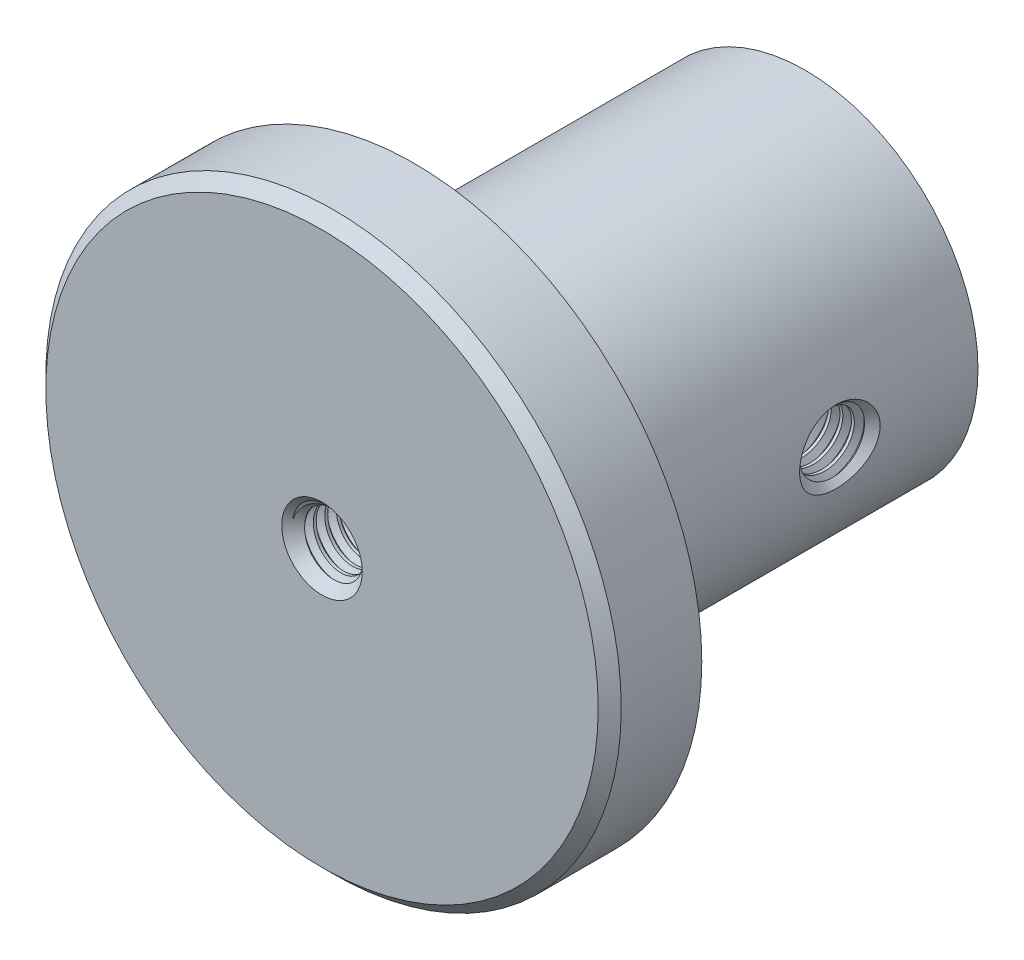
SolidWorks part; units mm, degrees
ref_plane "Front Plane" through (0, 0, 0) normal (0, 0, 1) x (1, 0, 0)
ref_plane "Top Plane" through (0, 0, 0) normal (0, 1, 0) x (1, 0, 0)
ref_plane "Right Plane" through (0, 0, 0) normal (1, 0, 0) x (0, 0, -1)
sketch "Sketch1" plane through (0, 0, 0) normal (0, 0, 1) x (1, 0, 0)
  circle A0 centre (0, 0) radius 12.5
  dimension "D1" = 25
extrude "Boss-Extrude1" add sketch "Sketch1" along normal blind 4
ref_axis "Axis1" through (0, 0, -0.35) along (0, 0, 1)
chamfer "Chamfer1" distance 0.5 angle 45 1 edges at (12.5, 0, 4)
ref_axis "Axis2" through (0, 14.0125, 4) along (0, -1, 0)
sketch "Sketch6" plane through (0, 0, 0) normal (1, 0, 0) x (0, 0, -1)
  line L0 (-4, 14.0125) -> (-4, -13.7625) construction
  line L1 (-4, 8.9) -> (-4, 11.1)
  line L2 (0, 12.5) -> (-3.5, 12.5) construction
  arc A0 (-4, 11.1) -> (-4, 8.9) centre (-4, 10) ccw
  dimension "D1" = 2.2
  dimension "D2" = 2.5
revolve "Cut-Revolve2" [suppressed] cut sketch "Sketch6" angle 360 about L1
pattern_circular "CirPattern1" [suppressed] count 15 over 360 of bodies 112
sketch "Sketch7" plane through (0, 0, 4) normal (0, 0, 1) x (1, 0, 0)
  circle A0 centre (0, 0) radius 1.25
  dimension "D1" = 2.5
extrude "Cut-Extrude1" cut sketch "Sketch7" against normal through all
thread "Thread1" pitch 0.5 method cut profile "Thread Profile1" start angle 0, offset 1, length 0, pitch 0.5, diameter 2.5
ref_plane "Plane1" through (-1.25, 0, 5) normal (0, -1, 0) x (-1, 0, 0)
sketch "Thread Profile1" plane through (-1.25, 0, 5) normal (0, -1, 0) x (-1, 0, 0)
  line L0 (0, 0) -> (0, 0.5) construction
  line L1 (0, 0) -> (0.2706, 0.1562)
  line L2 (0.2706, 0.1562) -> (0.2706, 0.2187)
  line L3 (0.2706, 0.2187) -> (0, 0.375)
  line L4 (0.2706, 0.1875) -> (0, 0.1875) construction
  line L11 (0, 0) -> (0, 0.375)
  point P2 (0, 0)
  dimension "Pitch" = 0.5
  dimension "Profile_Angle" = 60
  dimension "Profile_Land" = 0.0625
  dimension "Profile_Height" = 0.2706
sketch "Sketch10" plane through (0, 0, 4) normal (0, 0, 1) x (1, 0, 0)
  circle A0 centre (0, 0) radius 1.75
  dimension "D1" = 3.5
extrude "Cut-Extrude2" cut sketch "Sketch10" against normal blind 10 draft 45 contours A0
sketch "Sketch11" plane through (0, 0, 0) normal (0, 0, -1) x (-1, 0, 0)
  circle A0 centre (0, 0) radius 7.5
  dimension "D1" = 15
extrude "Boss-Extrude2" add sketch "Sketch11" along normal blind 17 contours A0
sketch "Sketch12" plane through (0, 0, -17) normal (0, 0, -1) x (-1, 0, 0)
  circle A0 centre (0, 0) radius 2.5
  dimension "D1" = 5
extrude "Cut-Extrude3" cut sketch "Sketch12" against normal blind 15 contours A0
ref_plane "Plane2" through (7.5, 0, 0) normal (1, 0, 0) x (0, 0, -1)
sketch "Sketch13" plane through (7.5, 0, 0) normal (1, 0, 0) x (0, 0, -1)
  line L0 (17, -7.5) -> (17, 7.5) construction
  circle A0 centre (11, 0) radius 1.25
  dimension "D2" = 2.5
  dimension "D1" = 6
extrude "Cut-Extrude4" cut sketch "Sketch13" against normal up to next contours A0
thread "Thread2" pitch 0.5 method cut profile "Thread Profile2" start angle 0, offset 1, length 8, pitch 0.5, diameter 2.5
ref_plane "Plane3" through (8.5, 0, -9.75) normal (0, -1, 0) x (0, 0, 1)
sketch "Thread Profile2" plane through (8.5, 0, -9.75) normal (0, -1, 0) x (0, 0, 1)
  line L0 (0, 0) -> (0, 0.5) construction
  line L1 (0, 0) -> (0.2706, 0.1562)
  line L2 (0.2706, 0.1562) -> (0.2706, 0.2187)
  line L3 (0.2706, 0.2187) -> (0, 0.375)
  line L4 (0.2706, 0.1875) -> (0, 0.1875) construction
  line L11 (0, 0) -> (0, 0.375)
  point P2 (0, 0)
  dimension "Pitch" = 0.5
  dimension "Profile_Angle" = 60
  dimension "Profile_Land" = 0.0625
  dimension "Profile_Height" = 0.2706
sketch "Sketch16" plane through (7.5, 0, 0) normal (1, 0, 0) x (0, 0, -1)
  circle A0 centre (11, 0) radius 1.75
  dimension "D1" = 3.5
extrude "Cut-Extrude5" cut sketch "Sketch16" against normal blind 15 draft 45
